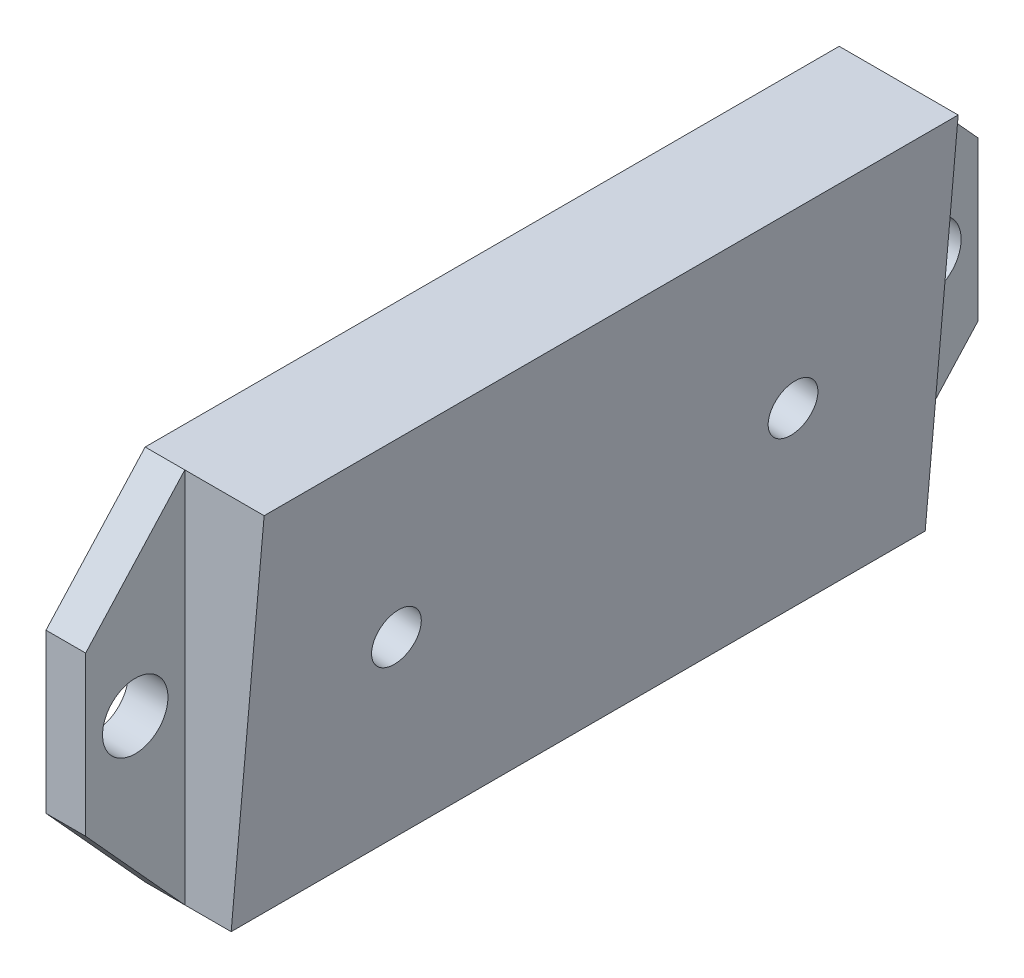
SolidWorks part; units mm, degrees
ref_plane "Płaszczyzna przednia" through (0, 0, 0) normal (0, 0, 1) x (1, 0, 0)
ref_plane "Płaszczyzna górna" through (0, 0, 0) normal (0, 1, 0) x (1, 0, 0)
ref_plane "Płaszczyzna prawa" through (0, 0, 0) normal (1, 0, 0) x (0, 0, -1)
sketch "Szkic1" plane through (0, 0, 0) normal (1, 0, 0) x (0, 0, -1)
  line L0 (0, 15) -> (70, 15) construction
  line L3 (0, 34) -> (70, 34)
  line L16 (35, 22) -> (35, 58.1386) construction
  line L25 (0, -4) -> (70, -4)
  line L26 (-10, 7) -> (-10, 23)
  line L27 (-10, 7) -> (0, -4)
  line L28 (-10, 23) -> (0, 34)
  line L29 (80, 7) -> (70, -4)
  line L30 (80, 7) -> (80, 23)
  line L31 (80, 23) -> (70, 34)
  point P7 (-10, 15)
  point P8 (35, -4)
  point P12 (35, 34)
  dimension "D1" = 19
  dimension "D2" = 8
extrude "Dodanie-wyciągnięcie1" add sketch "Szkic1" along normal blind 12
sketch "Szkic3" plane through (0, 0, 0) normal (-1, 0, 0) x (0, 0, 1)
  line L0 (-55, 15) -> (-15, 15) construction
  line L1 (-55, 20) -> (-15, 20)
  line L2 (-55, 10) -> (-15, 10)
  line L3 (-70, 34) -> (0, 34) construction
  arc A0 (-55, 20) -> (-55, 10) centre (-55, 15) ccw
  arc A1 (-15, 10) -> (-15, 20) centre (-15, 15) ccw
  point P2 (-35, 15)
  dimension "D1" = 19
  dimension "D4" = 5
  dimension "D2" = 35
  dimension "D3" = 40
extrude "Dodanie-wyciągnięcie2" add sketch "Szkic3" along normal blind 10
sketch "Szkic6" plane through (12, 0, 0) normal (1, 0, 0) x (0, 0, -1)
  line L0 (70, 34) -> (0, 34) construction
  line L2 (0, 34) -> (0, -4)
  line L4 (70, 34) -> (70, -4)
  line L5 (70, -4) -> (80, 7) construction
  line L6 (0, 34) -> (-10, 23)
  line L7 (-10, 23) -> (-10, 7)
  line L8 (-10, 7) -> (0, -4)
  line L9 (70, 34) -> (80, 23)
  line L10 (80, 23) -> (80, 7)
  line L11 (80, 7) -> (70, -4)
extrude "Wytnij-wyciągnięcie1" cut sketch "Szkic6" against normal blind 8
sketch "Szkic7" plane through (0, 0, 0) normal (0, 0, 1) x (1, 0, 0)
  line L0 (-5.599, 34) -> (-5.599, -167.1574) construction
  line L1 (-5.599, -167.1574) -> (12, 34) construction
  line L2 (-5.599, 34) -> (12, 34) construction
  line L3 (12, -4) -> (8.6754, -4)
  line L4 (12, -4) -> (4, -4) construction
  line L5 (8.6754, -4) -> (12, 34)
  line L6 (12, 34) -> (12, -4)
  dimension "D1" = 5
  dimension "D3" = 201.1574
extrude "Wytnij-wyciągnięcie2" cut sketch "Szkic7" against normal through all
hole_wizard "Otwór gwintowany M61" positions "Szkic 3D1" profile "Szkic8" tap size "M6" standard "ISO"
sketch3d "Szkic 3D1"
  line L6 (12, 34, -70) -> (12, 34, 0) construction
  line L7 (12, 34, -70) -> (8.6754, -4, -70) construction
  point P0 (10.344, 15.0723, -15)
  point P2 (10.344, 15.0723, -55)
  dimension "D1" = 40
  dimension "D2" = 19
  dimension "D3" = 19
  dimension "D4" = 15
sketch "Szkic8" plane through (10.344, 15.0723, -15) normal (0, 0, 1) x (0.0872, 0.9962, 0)
  line L0 (0, 0) -> (0, 15.5022)
  line L1 (0, 15.5022) -> (2.5, 14)
  line L2 (2.5, 14) -> (2.5, 0)
  line L5 (2.5, 0) -> (0, 0)
  line L10 (0, 15.5022) -> (-2.5, 14) construction
  line L11 (0, -6.35) -> (0, 107.95) construction
  dimension "Średnica wiertła gwintu" = 5
  dimension "Głębokość otworu gwintowanego" = 14
  dimension "Kąt wiertła" = 118
hole_wizard "Otwór pod śrubę M61" positions "Szkic 3D3" profile "Szkic11" hole size "M6" standard "ISO" end condition through all
sketch3d "Szkic 3D3"
  line L0 (4, -4, 0) -> (4, 34, 0) construction
  line L4 (4, 7, -80) -> (4, 23, -80) construction
  point P0 (4, 15, 5)
  point P2 (4, 15, -75)
  dimension "D1" = 5
  dimension "D4" = 5
sketch "Szkic11" plane through (4, 15, 5) normal (0, 1, 0) x (0, 0, -1)
  line L0 (0, 0) -> (0, 14)
  line L1 (0, 14) -> (3.3, 14)
  line L2 (3.3, 14) -> (3.3, 0)
  line L5 (3.3, 0) -> (0, 0)
  line L11 (0, -6.35) -> (0, 107.95) construction
  dimension "Średnica otworu na wylot" = 6.6
  dimension "Głębokość otworu na wylot" = 14
